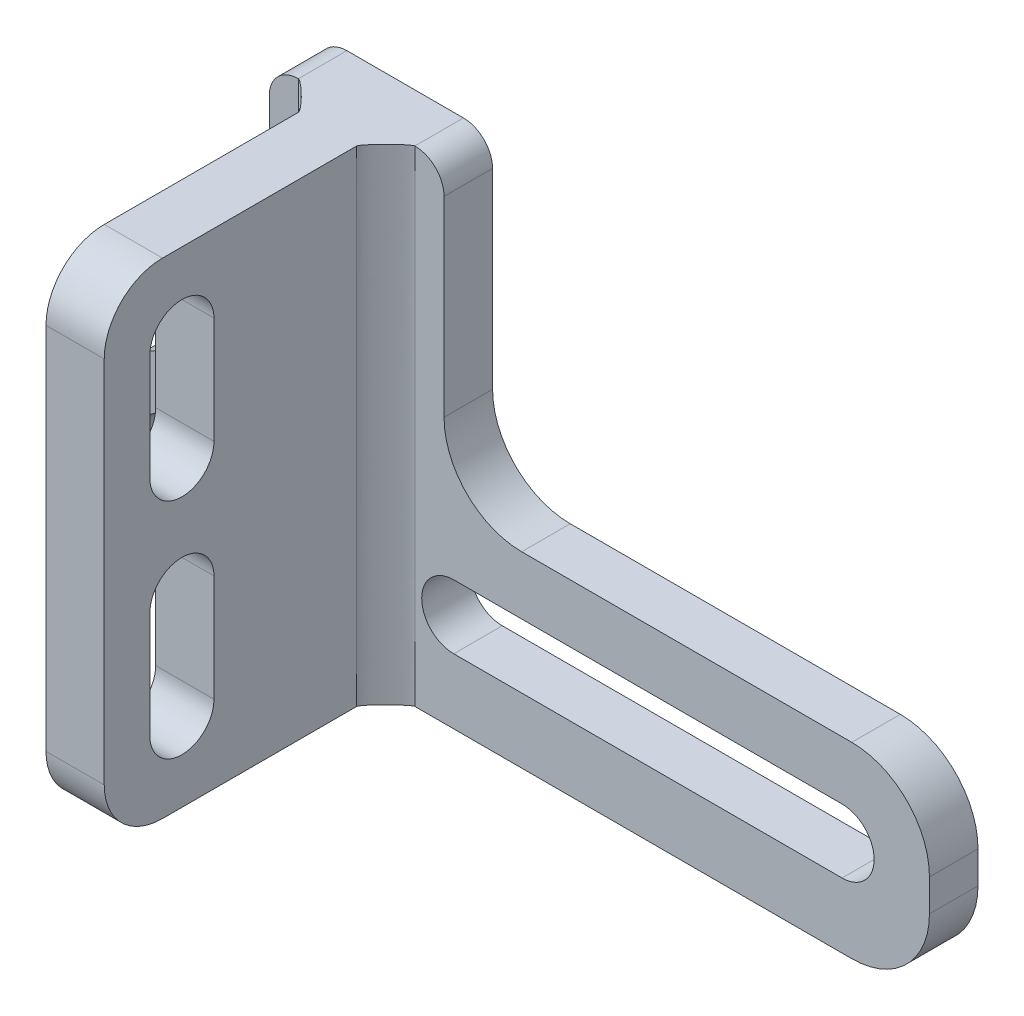
SolidWorks part; units mm, degrees
ref_plane "前视基准面" through (0, 0, 0) normal (0, 0, 1) x (1, 0, 0)
ref_plane "上视基准面" through (0, 0, 0) normal (0, 1, 0) x (1, 0, 0)
ref_plane "右视基准面" through (0, 0, 0) normal (1, 0, 0) x (0, 0, -1)
sketch "草图1" plane through (0, 0, 0) normal (0, 0, 1) x (1, 0, 0)
  line L1 (-21, -20) -> (21, -20)
  line L2 (-21, -20) -> (-21, 20)
  line L3 (-21, 20) -> (21, 20)
  line L4 (21, -20) -> (21, 20)
  line L5 (-21, -20) -> (21, 20) construction
  line L6 (-21, 20) -> (21, -20) construction
  point P0 (0, 0)
  dimension "D1" = 42
  dimension "D2" = 40
extrude "凸台-拉伸1" add sketch "草图1" along normal blind 2.5
sketch "草图2" plane through (0, 0, 2.5) normal (0, 0, 1) x (1, 0, 0)
  line L1 (-10, -5) -> (-7, -5)
  line L2 (-10, -5) -> (-10, 20)
  line L3 (-10, 20) -> (-7, 20)
  line L4 (-7, -5) -> (-7, 20)
  line L5 (-10, -5) -> (-7, 20) construction
  line L6 (-10, 20) -> (-7, -5) construction
  line L7 (21, 20) -> (-21, 20) construction
  point P0 (-8.5, 7.5)
  dimension "D1" = 3
  dimension "D2" = 7
  dimension "D3" = 25
extrude "凸台-拉伸2" add sketch "草图2" along normal blind 14.5
sketch "草图3" plane through (0, 0, 2.5) normal (0, 0, 1) x (1, 0, 0)
  line L0 (-12.2, 0) -> (12.2, 0) construction
  line L1 (0, 6.2294) -> (0, -3.9778) construction
  circle A0 centre (-13.7, 0) radius 1.5
  circle A1 centre (13.7, 0) radius 1.5
  dimension "D2" = 3
  dimension "D1" = 24.4
sketch "草图5" plane through (0, 0, 2.5) normal (0, 0, 1) x (1, 0, 0)
  line L0 (-18, 0) -> (-13.5, 0) construction
  line L1 (-12.2, 0) -> (12.2, 0) construction
  line L2 (-18, 1.65) -> (-13.5, 1.65)
  line L3 (-18, -1.65) -> (-13.5, -1.65)
  line L4 (-3.5, 0) -> (16.5, 0) construction
  line L5 (-3.5, 1.65) -> (16.5, 1.65)
  line L6 (-3.5, -1.65) -> (16.5, -1.65)
  line L7 (-10, 20) -> (-10, -5) construction
  line L8 (-7, -5) -> (-7, 20) construction
  arc A0 (-18, 1.65) -> (-18, -1.65) centre (-18, 0) ccw
  arc A1 (-13.5, -1.65) -> (-13.5, 1.65) centre (-13.5, 0) ccw
  arc A2 (-3.5, 1.65) -> (-3.5, -1.65) centre (-3.5, 0) ccw
  arc A3 (16.5, -1.65) -> (16.5, 1.65) centre (16.5, 0) ccw
  point P4 (-15.75, 0)
  point P9 (6.5, 0)
  dimension "D1" = 1.65
  dimension "D3" = 1.65
  dimension "D2" = 3.5
  dimension "D4" = 4.5
  dimension "D5" = 3.5
  dimension "D6" = 20
extrude "切除-拉伸2" cut sketch "草图5" against normal through all
sketch "草图4" plane through (-7, 0, 0) normal (1, 0, 0) x (0, 0, -1)
  line L0 (-13, 16) -> (-13, 10.5) construction
  line L1 (-11.35, 16) -> (-11.35, 10.5)
  line L2 (-14.65, 16) -> (-14.65, 10.5)
  line L3 (-17, -5) -> (-17, 20) construction
  line L4 (-17, 7.5) -> (0, 7.5) construction
  line L6 (-17, -5) -> (-17, 20) construction
  line L7 (-17, 20) -> (-2.5, 20) construction
  line L8 (0, -20) -> (0, 20) construction
  line L9 (-13, -1) -> (-13, 4.5) construction
  line L10 (-11.35, -1) -> (-11.35, 4.5)
  line L11 (-14.65, -1) -> (-14.65, 4.5)
  arc A0 (-11.35, 16) -> (-14.65, 16) centre (-13, 16) ccw
  arc A1 (-14.65, 10.5) -> (-11.35, 10.5) centre (-13, 10.5) ccw
  arc A2 (-11.35, -1) -> (-14.65, -1) centre (-13, -1) cw
  arc A3 (-14.65, 4.5) -> (-11.35, 4.5) centre (-13, 4.5) cw
  point P2 (-13, 13.25)
  point P19 (-13, 1.75)
  dimension "D1" = 1.65
  dimension "D2" = 3
  dimension "D3" = 4
  dimension "D4" = 4
extrude "切除-拉伸3" cut sketch "草图4" against normal through all
sketch "草图6" plane through (0, 0, 2.5) normal (0, 0, 1) x (1, 0, 0)
  line L0 (21, -20) -> (21, 20) construction
  line L1 (-21, -20) -> (21, -20)
  line L2 (-21, -20) -> (-21, -5)
  line L3 (-21, -5) -> (21, -5)
  line L4 (21, -20) -> (21, -5)
  line L5 (-10, -5) -> (-7, -5) construction
extrude "切除-拉伸4" cut sketch "草图6" against normal through all
sketch "草图7" plane through (0, 0, 2.5) normal (0, 0, 1) x (1, 0, 0)
  line L0 (-10, 20) -> (-10, -5) construction
  line L1 (-21, 20) -> (-13, 20)
  line L2 (-21, 20) -> (-21, 4.65)
  line L3 (-21, 4.65) -> (-17, 4.65)
  line L4 (-13, 20) -> (-13, 8.65)
  line L5 (21, 20) -> (-4, 20)
  line L6 (21, 20) -> (21, 4.65)
  line L7 (21, 4.65) -> (0, 4.65)
  line L8 (-4, 20) -> (-4, 8.65)
  line L9 (-13.5, 1.65) -> (-18, 1.65) construction
  line L10 (-7, -5) -> (-7, 20) construction
  arc A0 (0, 4.65) -> (-4, 8.65) centre (0, 8.65) cw
  arc A1 (-13, 8.65) -> (-17, 4.65) centre (-17, 8.65) cw
  dimension "D4" = 4
  dimension "D1" = 3
  dimension "D2" = 3
  dimension "D3" = 3
extrude "切除-拉伸5" cut sketch "草图7" against normal through all
fillet "圆角2" radius 3 2 edges at (-8.5, 20, 17) (-8.5, -5, 17)
fillet "圆角3" radius 1.5 2 edges
fillet "圆角4" radius 1.5 2 edges at (-4, 20, 1.25) (-13, 20, 1.25)
fillet "圆角5" radius 4 4 edges at (-21, -5, 1.25) (-21, 4.65, 1.25) (21, -5, 1.25) (21, 4.65, 1.25)
